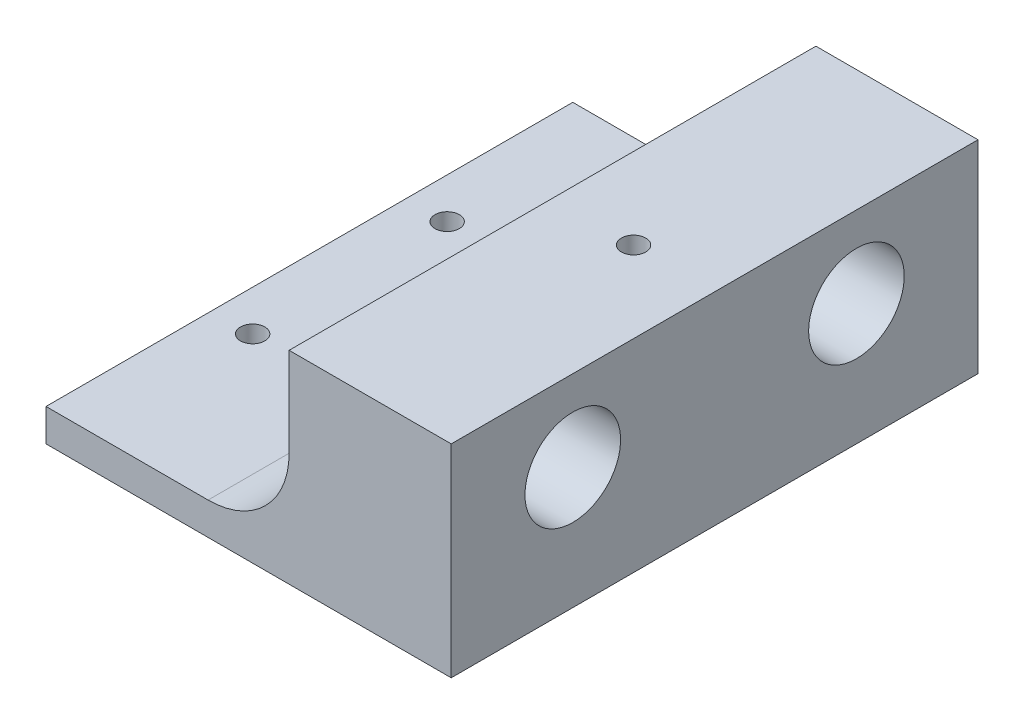
SolidWorks part; units mm, degrees
ref_plane "Front Plane" through (0, 0, 0) normal (0, 0, 1) x (1, 0, 0)
ref_plane "Top Plane" through (0, 0, 0) normal (0, 1, 0) x (1, 0, 0)
ref_plane "Right Plane" through (0, 0, 0) normal (1, 0, 0) x (0, 0, -1)
sketch "Sketch1" plane through (0, 0, 0) normal (0, 0, 1) x (1, 0, 0)
  line L0 (0, 0) -> (0, 25) construction
  line L2 (-40, 0) -> (-40, 4)
  line L3 (-40, 4) -> (-20, 4)
  line L4 (-10, 14) -> (-10, 25)
  line L5 (-10, 25) -> (10, 25)
  line L6 (10, 14) -> (10, 25)
  line L9 (10, 14) -> (10, 0)
  line L10 (10, 0) -> (-40, 0)
  arc A0 (-20, 4) -> (-10, 14) centre (-20, 14) ccw
  point P13 (-10, 4)
  point P16 (10, 4)
  dimension "D4" = 10
  dimension "D1" = 25
  dimension "D2" = 50
  dimension "D3" = 20
  dimension "D6" = 4
extrude "Boss-Extrude1" add sketch "Sketch1" along normal mid plane 65
sketch "Sketch2" plane through (10, 0, 0) normal (1, 0, 0) x (0, 0, -1)
  line L0 (0, 0) -> (0, 25) construction
  line L1 (-32.5, 0) -> (32.5, 0) construction
  line L2 (-32.5, 25) -> (32.5, 25) construction
  circle A0 centre (-17.5, 15) radius 5.9
  circle A1 centre (17.5, 15) radius 5.9
  dimension "D1" = 11.8
  dimension "D2" = 35
  dimension "D3" = 15
extrude "Cut-Extrude1" cut sketch "Sketch2" against normal through all both and the other way through all
sketch "Sketch3" plane through (0, 0, 0) normal (0, -1, 0) x (1, 0, 0)
  line L0 (-35, -32.5) -> (-35, 32.5) construction
  line L1 (-40, -32.5) -> (10, -32.5) construction
  line L2 (-40, 32.5) -> (10, 32.5) construction
  line L3 (0, 0) -> (-40, 0) construction
  line L4 (-40, 32.5) -> (-40, -32.5) construction
  circle A0 centre (-35, 12) radius 1.5
  circle A1 centre (-35, -12) radius 1.5
  dimension "D1" = 3
  dimension "D3" = 24
  dimension "D2" = 5
extrude "Cut-Extrude2" cut sketch "Sketch3" against normal through all both and the other way through all
sketch "Sketch4" plane through (0, 25, 0) normal (0, 1, 0) x (1, 0, 0)
  line L0 (0, -32.5) -> (0, 32.5) construction
  line L1 (10, -32.5) -> (-10, -32.5) construction
  line L2 (10, 32.5) -> (-10, 32.5) construction
  line L3 (10, -32.5) -> (10, 32.5) construction
  circle A0 centre (0, 0) radius 1.5
  dimension "D1" = 3
  dimension "D2" = 10
extrude "Cut-Extrude3" cut sketch "Sketch4" against normal through all both and the other way through all
